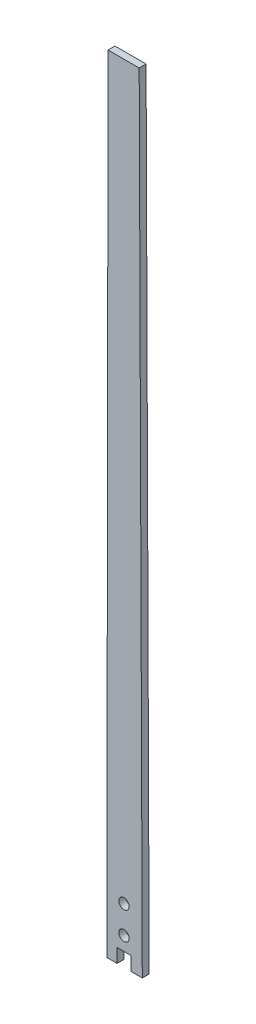
SolidWorks part; units mm, degrees
material "6061-T6 (SS)"
ref_plane "XY" through (0, 0, 0) normal (0, 0, 1) x (1, 0, 0)
ref_plane "XZ" through (0, 0, 0) normal (0, 1, 0) x (1, 0, 0)
ref_plane "YZ" through (0, 0, 0) normal (1, 0, 0) x (0, 0, -1)
ref_axis "X" through (-7.8995, 0, 0) along (1, 0, 0)
ref_axis "Y" through (0, -19.9998, 0) along (0, 1, 0)
ref_axis "Z" through (0, 0, 3.3337) along (0, 0, -1)
sketch "Sketch1" plane through (0, 0, 0) normal (0, 0, 1) x (1, 0, 0)
  line L0 (-5.3354, 399.996) -> (10.3597, 399.996)
  arc B0 (10.4977, 29.9643) -> (-5.8638, 31.2038) centre (0, 0) ccw
  spline B1 degree 3 poles (-5.2871, 399.996) (-5.392, 338.6022) (-5.5295, 254.0955) (-5.7181, 131.1648) (-5.8086, 69.6278) (-5.8638, 31.2038) knots 0 0 0 0 0.499418 0.687434 1 1 1 1
  spline B2 degree 3 poles (10.4977, 29.9643) (10.3579, 67.799) (10.0202, 157.8026) (9.6677, 247.8061) (9.323, 333.3153) (9.1861, 366.6557) (9.0464, 399.996) knots 0 0 0 0 0.306741 0.729696 0.729696 1 1 1 1
sketch_block_instance "Block2-3"
sketch_block "Block2"
sketch "Sketch2" plane through (0, 0, 0) normal (0, 0, 1) x (1, 0, 0)
  line L5 (-5.3354, 399.996) -> (10.3597, 399.996) construction
  line L6 (-5.2871, 399.996) -> (9.0464, 399.996)
  arc A0 (11.1829, 29.7154) -> (-6.1429, 31.1501) centre (0, 0) ccw construction
  arc A1 (11.1829, 29.7154) -> (-6.1429, 31.1501) centre (0, 0) ccw construction
  arc A2 (10.4977, 29.9643) -> (-5.8638, 31.2038) centre (0, 0) ccw construction
  arc A3 (10.4977, 29.9643) -> (-5.8638, 31.2038) centre (0, 0) ccw
  spline S2 degree 3 poles (17.7702, -1970.0203) (14.5579, -1265.5276) (12.6307, -508.8588) (9.6677, 247.8061) (6.6351, 999.9719) (2.7265, 1699.9645) (-4.9943, 2399.9361) knots -5.4049 -5.4049 -5.4049 -5.4049 0.306741 0.729696 0.729696 6.404863 6.404863 6.404863 6.404863 only from (10.4977, 29.9643) to (9.0464, 399.996) construction
  spline S3 degree 3 poles (0.8769, 2399.9691) (-2.7293, 1671.9207) (-4.5067, 920.7552) (-6.741, -535.4974) (-7.3087, -1263.6973) (-8.5444, -1968.7825) knots -5.423052 -5.423052 -5.423052 -5.423052 0.499418 0.687434 6.423072 6.423072 6.423072 6.423072 only from (-5.2871, 399.996) to (-5.8638, 31.2038) construction
  spline S4 degree 3 poles (1.6959, 2399.9709) (-2.5375, 1681.4281) (-4.5801, 926.5114) (-7.1376, -529.7526) (-7.821, -1267.4681) (-8.7186, -1968.8137) knots -5.422272 -5.422272 -5.422272 -5.422272 0.422034 0.717837 6.422218 6.422218 6.422218 6.422218 only from (-5.4852, 399.996) to (-6.1429, 31.1501) construction
  spline S5 degree 3 poles (18.4955, -1970.2601) (15.5733, -1262.7892) (13.5923, -527.295) (10.4368, 208.1943) (10.1958, 263.5082) (7.0079, 984.7428) (2.3917, 1705.971) (-9.8125, 2399.8596) knots -5.401234 -5.401234 -5.401234 -5.401234 0.330685 0.557672 0.557672 0.778836 6.401091 6.401091 6.401091 6.401091 only from (11.1829, 29.7154) to (9.5778, 399.996) construction
  spline S6 degree 3 poles (-5.4852, 399.996) (-5.5861, 348.1074) (-5.7509, 259.8504) (-5.9668, 136.9018) (-6.086, 65.8417) (-6.1429, 31.1501) knots 0 0 0 0 0.422034 0.717837 1 1 1 1 construction
  spline S7 degree 3 poles (11.1829, 29.7154) (11.0171, 70.5308) (10.7321, 139.3626) (10.4368, 208.1943) (10.1958, 263.5082) (9.9545, 318.1033) (9.705, 372.6985) (9.5778, 399.996) knots 0 0 0 0 0.330685 0.557672 0.557672 0.778836 1 1 1 1 construction
  spline S8 degree 3 poles (10.4977, 29.9643) (10.3579, 67.799) (10.0202, 157.8026) (9.6677, 247.8061) (9.323, 333.3153) (9.1861, 366.6557) (9.0464, 399.996) knots 0 0 0 0 0.306741 0.729696 0.729696 1 1 1 1
  spline S9 degree 3 poles (-5.2871, 399.996) (-5.392, 338.6022) (-5.5295, 254.0955) (-5.7181, 131.1648) (-5.8086, 69.6278) (-5.8638, 31.2038) knots 0 0 0 0 0.499418 0.687434 1 1 1 1
  point P0 (0, 0)
  point P6 (-5.2864, 400.3759)
  point P11 (-5.2483, 399.996)
  point P14 (0, 0)
  point P15 (9.0052, 399.996)
  point P17 (-5.2871, 399.996)
extrude "Boss-Extrude1" add sketch "Sketch2" along normal blind 3.175
sketch "Sketch3" plane through (0, 0, 0) normal (0, 0, 1) x (1, 0, 0)
  line L0 (0, 0) -> (2.032, 0) construction
  line L1 (-9.398, 0) -> (13.462, 0)
  line L2 (-9.398, 0) -> (-9.398, 38.1)
  line L3 (-9.398, 38.1) -> (-1.143, 38.1)
  line L4 (13.462, 0) -> (13.462, 38.1)
  line L6 (5.207, 38.1) -> (5.207, 44.45)
  line L7 (5.207, 44.45) -> (-1.143, 44.45)
  line L8 (-1.143, 38.1) -> (-1.143, 44.45)
  line L9 (2.032, 0) -> (2.032, 38.1) construction
  line L10 (5.207, 38.1) -> (13.462, 38.1)
  line L11 (-1.143, 38.1) -> (5.207, 38.1) construction
  circle A0 centre (0, 0) radius 31.75 construction
  point P8 (-5.854, 38.0015)
  point P18 (10.4683, 37.9232)
  point P21 (2.3984, 39.0203)
  dimension "D1" = 63.5
  dimension "D2" = 38.1
  dimension "D3" = 2.032
  dimension "D4" = 6.35
  dimension "D5" = 6.35
  dimension "D6" = 22.86
extrude "Cut-Extrude2" cut sketch "Sketch3" against normal through all and the other way through all
hole_wizard "3/16 (0.1875) Dowel Hole1" positions "Sketch4" profile "Sketch5" hole size "3/16" standard "ANSI Inch"
sketch "Sketch4" plane through (0, 0, 3.175) normal (0, 0, 1) x (1, 0, 0)
  line L0 (2.032, 44.45) -> (2.032, 50.8) construction
  line L1 (5.207, 44.45) -> (-1.143, 44.45) construction
  line L2 (2.032, 50.8) -> (2.032, 63.5) construction
  point P0 (2.032, 50.8)
  point P2 (2.032, 63.5)
  point P13 (2.032, 63.5)
  point P14 (0.3156, 50.8)
  dimension "D1" = 6.35
  dimension "D2" = 12.7
sketch "Sketch5" plane through (2.032, 50.8, 3.175) normal (1, 0, 0) x (0, -1, 0)
  line L0 (0, 0) -> (0, 12.0988)
  line L1 (0, 12.0988) -> (2.3812, 10.668)
  line L2 (2.3812, 10.668) -> (2.3812, 0)
  line L5 (2.3812, 0) -> (0, 0)
  line L10 (0, 12.0988) -> (-2.3813, 10.668) construction
  line L11 (0, -6.35) -> (0, 107.95) construction
  dimension "Hole Dia." = 4.7625
  dimension "Hole Depth" = 10.668
  dimension "Drill Angle" = 118
